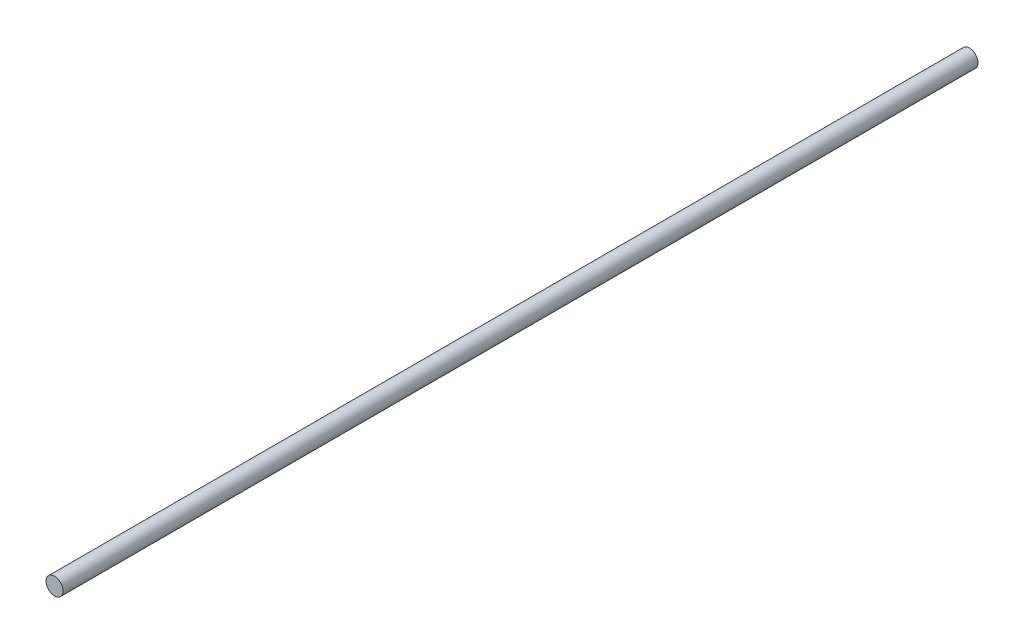
SolidWorks part; units mm, degrees
material "AISI 316 Stainless Steel Sheet (SS)"
ref_plane "Front (1)" through (0, 0, 0) normal (0, 0, 1) x (1, 0, 0)
ref_plane "Top (2)" through (0, 0, 0) normal (0, 1, 0) x (1, 0, 0)
ref_plane "Right (3)" through (0, 0, 0) normal (1, 0, 0) x (0, 0, -1)
ref_axis "X Axis" through (13.5064, 0, 0) along (-1, 0, 0)
ref_axis "Y Axis" through (0, 12.3593, 0) along (0, -1, 0)
ref_axis "Z Axis" through (0, 0, 14.1119) along (0, 0, -1)
sketch "Sketch2" plane through (0, 0, 0) normal (1, 0, 0) x (0, 0, -1)
  line L1 (0, 0) -> (427.6, 0)
  line L2 (0, 0) -> (0, 4)
  line L3 (0, 4) -> (427.6, 4)
  line L4 (427.6, 0) -> (427.6, 4)
  dimension "D1" = 427.6
  dimension "D2" = 4
revolve "Revolve1" add sketch "Sketch2" angle 360 about L1
cosmetic thread "Cosmetic Thread2"
